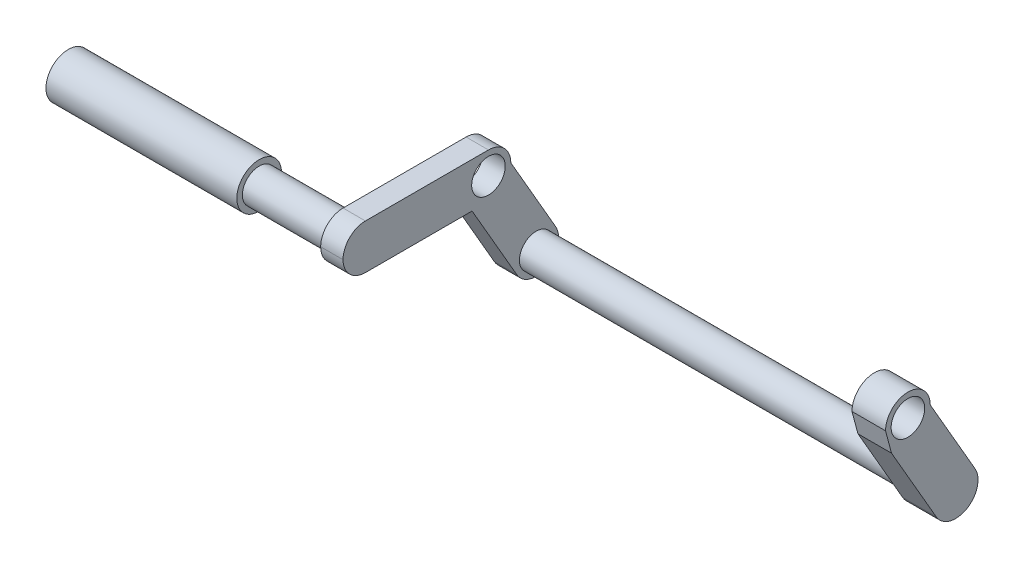
SolidWorks part; units mm, degrees
material "Nickel"
ref_plane "Front Plane" through (0, 0, 0) normal (0, 0, 1) x (1, 0, 0)
ref_plane "Top Plane" through (0, 0, 0) normal (0, 1, 0) x (1, 0, 0)
ref_plane "Right Plane" through (0, 0, 0) normal (1, 0, 0) x (0, 0, -1)
sketch "Sketch2" plane through (0, 0, 0) normal (1, 0, 0) x (0, 0, -1)
  circle A0 centre (0, 0) radius 2
  dimension "D1" = 4
extrude "Boss-Extrude1" add sketch "Sketch2" along normal blind 17.06
sketch "Sketch3" plane through (17.06, 0, 0) normal (1, 0, 0) x (0, 0, -1)
  circle A0 centre (0, 0) radius 1.5
  dimension "D1" = 3
extrude "Boss-Extrude2" add sketch "Sketch3" along normal blind 9.5
sketch "Sketch4" plane through (26.56, 0, 0) normal (1, 0, 0) x (0, 0, -1)
  line L1 (-2, 2) -> (1.9881, 2)
  line L2 (-2, 2) -> (-2, -2)
  line L3 (-2, -2) -> (1.9881, -2)
  line L4 (1.9881, 2) -> (1.9881, -2)
  circle A0 centre (0, 0) radius 2 construction
extrude "Boss-Extrude3" add sketch "Sketch4" against normal blind 2
sketch "Sketch5" plane through (0, 0, 2) normal (0, 0, 1) x (1, 0, 0)
  line L1 (26.56, 2) -> (24.56, 2)
  line L2 (26.56, 2) -> (26.56, -2)
  line L3 (26.56, -2) -> (24.56, -2)
  line L4 (24.56, 2) -> (24.56, -2)
extrude "Boss-Extrude4" add sketch "Sketch5" against normal blind 15
fillet "Fillet1" radius 2 1 edges at (25.56, 2, 2)
fillet "Fillet2" radius 2 1 edges at (25.56, -2, 2)
fillet "Fillet3" radius 2 2 edges at (25.56, -2, -13) (25.56, 2, -13)
sketch "Sketch6" plane through (26.56, 0, 0) normal (1, 0, 0) x (0, 0, -1)
  circle A0 centre (11, 0) radius 1.5
  point P2 (0, 0)
  dimension "D1" = 3
  dimension "D2" = 11
extrude "Cut-Extrude1" cut sketch "Sketch6" against normal through all
sketch "Sketch7" plane through (26.56, 0, 0) normal (1, 0, 0) x (0, 0, -1)
  line L0 (13, 0) -> (18, -8.6603)
  line L1 (9.5359, -2) -> (14.5359, -10.6603)
  line L2 (0, -2) -> (11, -2) construction
  line L3 (9.5359, -2) -> (11, -2)
  line L4 (14.5359, -10.6603) -> (18, -8.6603)
  line L6 (0, -2) -> (11, -2)
  line L7 (11, 2) -> (0, 2)
  line L8 (0, -2) -> (9.5359, -2)
  line L9 (11, 2) -> (0, 2)
  circle A0 centre (11, 0) radius 2
  arc A4 (11, -2) -> (13, 0) centre (11, 0) ccw
  arc A5 (13, 0) -> (11, 2) centre (11, 0) ccw
  arc A6 (0, 2) -> (-2, 0) centre (0, 0) ccw
  arc A7 (-2, 0) -> (0, -2) centre (0, 0) ccw
  arc A9 (13, 0) -> (11, 2) centre (11, 0) ccw
  arc A10 (0, 2) -> (-2, 0) centre (0, 0) ccw
  arc A11 (-2, 0) -> (0, -2) centre (0, 0) ccw
  line M11 (0, -2) -> (11, -2)
  arc M12 (11, -2) -> (13, 0) centre (11, 0) ccw
  dimension "D4" = 120
  dimension "D1" = 4
  dimension "D2" = 10
  dimension "D3" = 0
extrude "Boss-Extrude5" add sketch "Sketch7" against normal blind 2 contours L1 L4 L0 M12 M11 region at (26.56, -5.6137, -13.9182)
fillet "Fillet4" radius 2 1 edges at (25.56, -8.6603, -18)
fillet "Fillet5" radius 2 1 edges at (25.56, -10.6603, -14.5359)
sketch "Sketch8" plane through (26.56, 0, 0) normal (1, 0, 0) x (0, 0, -1)
  circle A0 centre (15.2679, -7.9282) radius 1.5
  arc A1 (16.2679, -9.6603) -> (17, -6.9282) centre (15.2679, -7.9282) ccw construction
  point P2 (16.6789, -5.7621)
  dimension "D1" = 3
extrude "Boss-Extrude6" add sketch "Sketch8" along normal blind 36
sketch "Sketch9" plane through (62.56, 0, 0) normal (1, 0, 0) x (0, 0, -1)
  line L0 (17, -6.9282) -> (13, 0)
  line L1 (9.5359, -2) -> (13.5359, -8.9282)
  line L2 (9.5359, -2) -> (9, 0)
  circle A0 centre (15.2679, -7.9282) radius 2
  circle A1 centre (11, 0) radius 2
  circle A2 centre (11, 0) radius 1.5
  circle M1 centre (15.2679, -7.9282) radius 1.5
  dimension "D1" = 3
extrude "Boss-Extrude7" add sketch "Sketch9" along normal blind 1.5 and the other way blind 1.5 contours A0 M1 | A1 L2 L1 A0 L0 | A1 L2 A2 | M1 region at (62.56, -4.0464, -12.9754) region at (62.56, -7.4252, -17.1452) region at (62.56, -1.8772, -11.503) region at (62.56, -7.9282, -15.2679)
